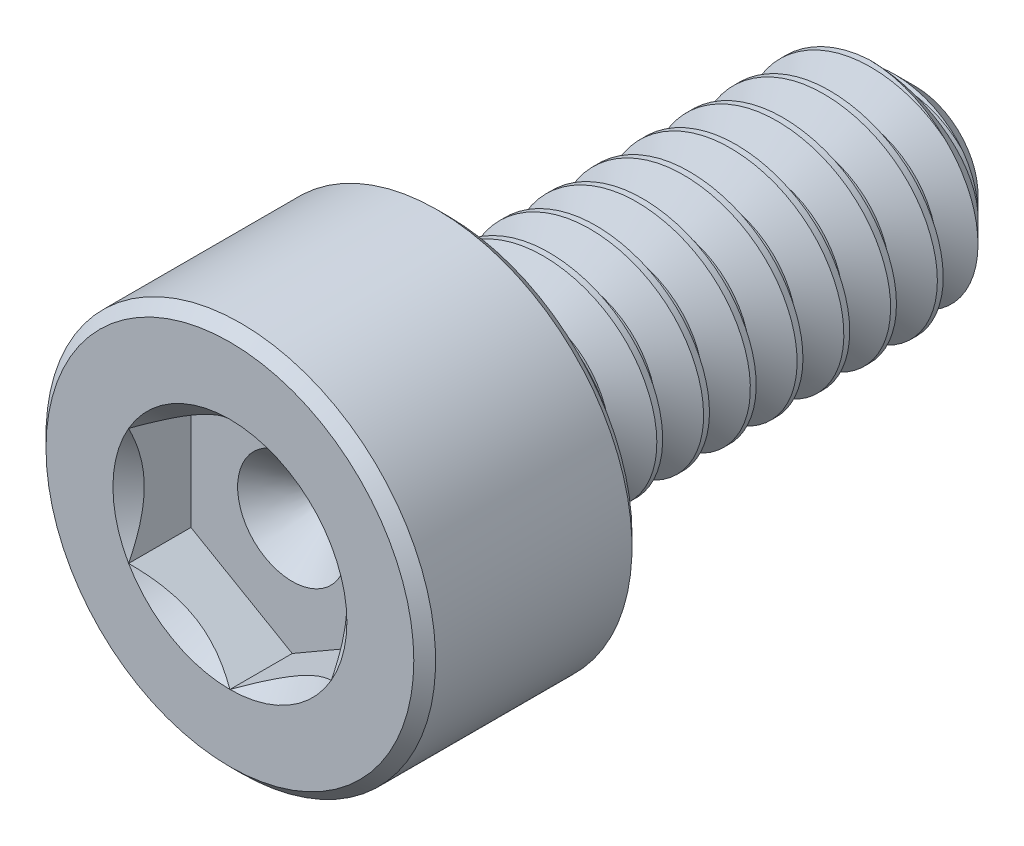
SolidWorks part; units mm, degrees
ref_plane "Front Plane" through (0, 0, 0) normal (0, 0, 1) x (1, 0, 0)
ref_plane "Top Plane" through (0, 0, 0) normal (0, 1, 0) x (1, 0, 0)
ref_plane "Right Plane" through (0, 0, 0) normal (1, 0, 0) x (0, 0, -1)
sketch "Sketch1" plane through (0, 0, 0) normal (1, 0, 0) x (0, 0, -1)
  line L0 (-2.2, 0) -> (2.2, 0) construction
  line L1 (2.2, 0) -> (2.2, 0.4) construction
  line L2 (2.2, 0.4) -> (1.9, 0.7) construction
  line L3 (1.9, 0.7) -> (1.975, 0.7) construction
  line L4 (1.975, 0.7) -> (-0.8, 0.7) construction
  line L5 (-0.8, 0.7) -> (-0.8, 1.25) construction
  line L6 (-0.8, 1.25) -> (-2.2, 1.25) construction
  line L7 (-2.2, 1.25) -> (-2.2, 0) construction
  line L8 (2.2, 0.4) -> (2.2, 0.7) construction
  line L9 (2.1812, 0.7325) -> (2.3312, 0.4727) construction
  line L10 (2.3312, 0.4727) -> (2.4812, 0.7325) construction
  line L11 (2.4812, 0.7325) -> (2.1812, 0.7325) construction
  line L12 (2.3312, 0.7325) -> (2.3312, 0.7) construction
  line L13 (2.3312, 0.4727) -> (2.3312, 0.5051) construction
  line L14 (2.3125, 0.5051) -> (2.35, 0.5051) construction
  line L15 (2.2, 0.7) -> (2.4625, 0.7) construction
  line L16 (2.1906, 0.7162) -> (2.4719, 0.7162) construction
  line L17 (2.2, 0) -> (2.2, -0.7) construction
  line L18 (-0.87, 1.25) -> (-0.8, 1.18) construction
  line L19 (-2.13, 1.25) -> (-2.2, 1.18) construction
  line L20 (-0.8, 0.7) -> (-0.8, 0) construction
  line L21 (-0.8, 0.35) -> (0.2, 0.35) construction
  line L22 (0.2, 0.35) -> (1.2, 0.35) construction
  line L23 (1.2, 0.35) -> (2.2, 0.35) construction
  line L24 (0.2, 0.35) -> (0.2, 0.7) construction
  line L25 (0.2, 0.7) -> (0.2, 1.25) construction
  line L26 (1.2, 0.35) -> (1.2, 1.25) construction
  point P0 (-2.2, 0.65)
  point P3 (1.45, 0.7)
  point P4 (0, 0)
  point P18 (1.2, 0.7)
  point P22 (2.3312, 0.5051)
  point P24 (1.975, 0.7)
  point P25 (2.3312, 0.7)
  point P28 (2.3312, 0.7162)
  point P29 (1.45, -0.7)
  point P30 (0.2, 0.7)
  point P31 (-1.5, 1.25)
  point P37 (-1.045, 1.25)
  point P38 (-2.095, 1.25)
  point P45 (0.2, 0.35)
  point P46 (1.2, 0.35)
  dimension "D1" = 45
  dimension "D2" = 0.0375
  dimension "D3" = 0.3
  dimension "D7" = 0.07
  dimension "D8" = 0.07
  dimension "D9" = 0.07
  dimension "D10" = 0.035
  dimension "D11" = 0.175
  dimension "Drive Size" = 1.3
  dimension "Head Diameter" = 2.5
  dimension "Head Height" = 1.4
  dimension "Thread Pitch" = 0.3
  dimension "Thread Major Diameter" = 1.4
  dimension "Length" = 3
  dimension "D12" = 0.225
  dimension "D4" = 0.75
sketch "Sketch2" plane through (0, 0, 0) normal (1, 0, 0) x (0, 0, -1)
  line L0 (-2.2, 0) -> (-2.2, 1.18)
  line L1 (-2.13, 1.25) -> (-0.87, 1.25)
  line L2 (-0.8, 1.18) -> (-0.8, 0.7)
  line L3 (-0.8, 0.7) -> (1.9, 0.7)
  line L4 (1.9, 0.7) -> (2.2, 0.4)
  line L5 (2.2, 0.4) -> (2.2, 0)
  line L6 (-0.87, 1.25) -> (-0.8, 1.18) construction
  line L7 (2.2, 0) -> (-2.2, 0)
  line L8 (-2.13, 1.25) -> (-2.2, 1.18) construction
  line L9 (-0.87, 1.25) -> (-0.8, 1.18)
  line L10 (-2.13, 1.25) -> (-2.2, 1.18)
revolve "Revolve1" add sketch "Sketch2" angle 360 about L7
sketch "Sketch3" plane through (0, 0, 2.2) normal (0, 0, 1) x (1, 0, 0)
  line L1 (0.65, -0.3753) -> (0.65, 0.3753)
  line L2 (0.65, 0.3753) -> (0, 0.7506)
  line L3 (0, 0.7506) -> (-0.65, 0.3753)
  line L4 (-0.65, 0.3753) -> (-0.65, -0.3753)
  line L5 (-0.65, -0.3753) -> (0, -0.7506)
  line L6 (0, -0.7506) -> (0.65, -0.3753)
  circle A0 centre (0, 0) radius 0.65 construction
extrude "Cut-Extrude1" cut sketch "Sketch3" against normal offset from surface (0.4 mm away) 1 up to face at (0, 1.18, 0.8)
sketch "Sketch4" plane through (0, 0, 2.2) normal (0, 0, 1) x (1, 0, 0)
  circle A0 centre (0, 0) radius 0.7506
extrude "Cut-Extrude2" cut sketch "Sketch4" against normal up to vertex (0.7 mm away) draft 45 up to point (0, 1.25, 1.5)
ref_plane "Plane1" through (0, 0, -1.975) normal (0, 0, 1) x (1, 0, 0)
split "Split1" bodies to split 106 resulting bodies 107 108 split by face at (0, 1.18, 0.8)
sketch "Sketch6" plane through (0, 0, -2.2) normal (0, 0, -1) x (-1, 0, 0)
  circle A0 centre (0, 0) radius 0.7
curve "Helix/Spiral1" pitch 0.3 height 3.345 radius 0.7 centre (0, 0, -2.2) axis (0, 0, 1) start towards (0, 1, 0)
sketch "Sketch7" plane through (0, 0, 0) normal (1, 0, 0) x (0, 0, -1)
  line L0 (2.1906, 0.7162) -> (2.4719, 0.7162)
  line L1 (2.4719, 0.7162) -> (2.35, 0.5051)
  line L2 (2.35, 0.5051) -> (2.3125, 0.5051)
  line L3 (2.3125, 0.5051) -> (2.1906, 0.7162)
sweep "Cut-Sweep1" cut profiles "Sketch7" path "Helix/Spiral1" align with end faces yes
sketch "Sketch8" plane through (0, 0, 0.8) normal (0, 0, -1) x (-1, 0, 0)
  circle A0 centre (0, 0) radius 0.7
extrude "Boss-Extrude1" add sketch "Sketch8" along normal through all draft 45
equation "\"D2@Sketch1\" = \"Thread Pitch@Sketch1\" / 8"
equation "\"D3@Sketch1\"= \"Thread Pitch@Sketch1\""
equation "\"D4@Helix/Spiral1\" = \"Thread Pitch@Sketch1\""
equation "\"D7@Sketch1\" = \"Head Height@Sketch1\" * .05"
equation "\"D8@Sketch1\"=\"D7@Sketch1\""
equation "\"D9@Sketch1\"=\"D7@Sketch1\""
equation "\"D10@Sketch1\"=\"D7@Sketch1\"/2"
equation "\"D11@Sketch1\"=\"D10@Sketch1\"*5"
equation "\"D4@Sketch1\"=\"Thread Pitch@Sketch1\"*2.5"
equation "\"D12@Sketch1\"=\"Thread Pitch@Sketch1\"*.75"
